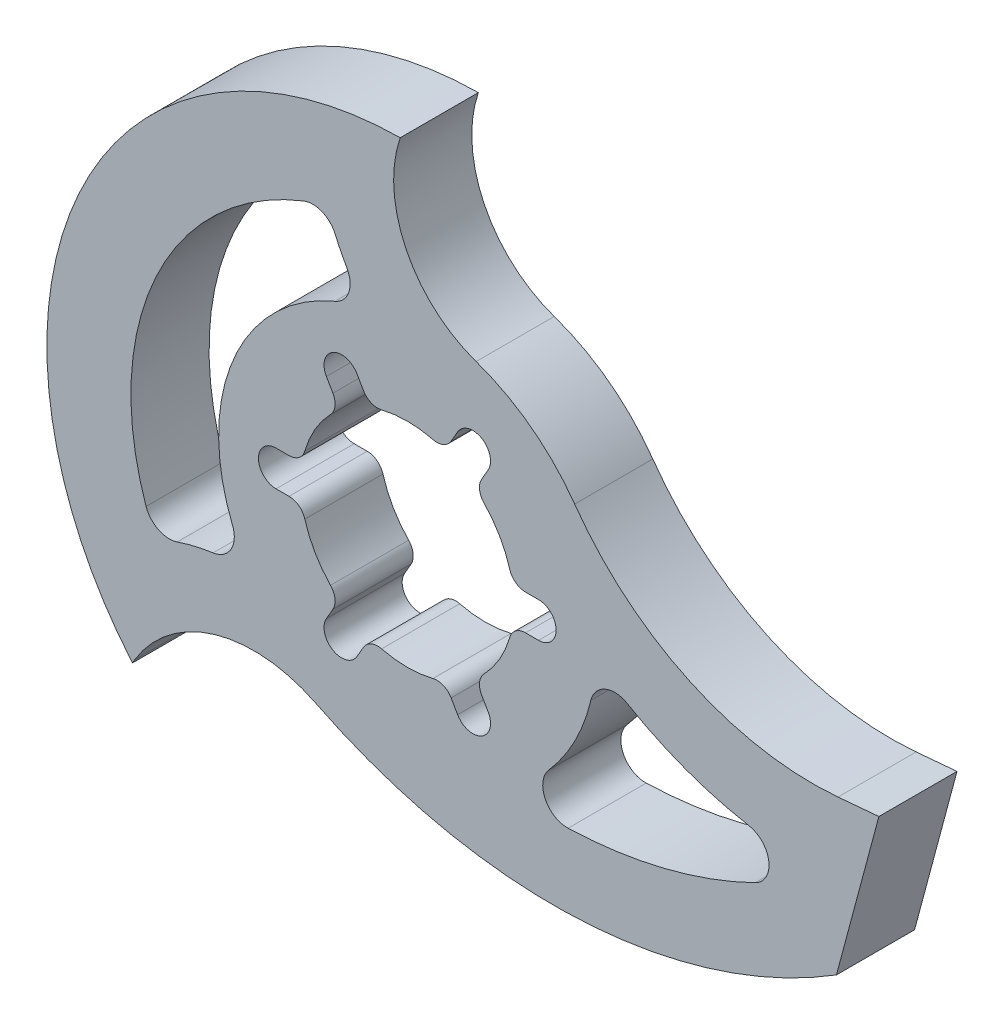
SolidWorks part; units mm, degrees
material "Alloy Steel"
ref_plane "Front Plane" through (0, 0, 0) normal (0, 0, 1) x (1, 0, 0)
ref_plane "Top Plane" through (0, 0, 0) normal (0, 1, 0) x (1, 0, 0)
ref_plane "Right Plane" through (0, 0, 0) normal (1, 0, 0) x (0, 0, -1)
sketch "Sketch1" plane through (0, 0, 0) normal (0, 0, 1) x (1, 0, 0)
  line L0 (0, 0) -> (57.5, 0) construction
  line L1 (57.5, 0) -> (52.3236, -19.3185)
  line L2 (0, 0) -> (-40.042, 16.9968) construction
  line L3 (0, 0) -> (-0.861, 42.4913) construction
  line L4 (0, 0) -> (-33.5025, -29.2888) construction
  line L5 (57.5, 0) -> (52.519, -0.4358)
  line L6 (-33.5025, -29.2888) -> (-36.2461, -34.2713) construction
  line L7 (-0.861, 42.4913) -> (1.5534, 49.5674) construction
  circle A0 centre (0, 0) radius 57.5 construction
  circle A2 centre (0, 0) radius 16 construction
  circle A3 centre (0, 0) radius 13 construction
  circle A4 centre (0, 0) radius 44.5 construction
  arc A5 (-0.861, 42.4913) -> (-33.5025, -29.2888) centre (-0.4386, -1.0126) ccw
  arc A6 (-33.5025, -29.2888) -> (-33.235, -28.8228) centre (-20.3629, -36.5241) cw
  arc A7 (-0.861, 42.4913) -> (8.3945, 23.4847) centre (13.3355, 37.6476) ccw
  arc A8 (52.519, -0.4358) -> (20.4072, 14.4411) centre (49.4212, 34.9727) cw
  arc A9 (-33.235, -28.8228) -> (-11.1617, -22.37) centre (-18.7157, -37.5095) cw
  arc A10 (-11.1617, -22.37) -> (52.3236, -19.3185) centre (17.8587, 35.792) ccw
  circle A11 centre (0, 0) radius 25 construction
  arc A12 (8.3945, 23.4847) -> (20.4072, 14.4411) centre (0.2673, 0.1892) cw
  point P3 (51.4405, -19.3185)
  point P6 (-9.7502, -22.7382)
  point P27 (0, 0)
  point P28 (7.4098, 24.0096)
  point P30 (-5.8116, -21.7365)
  point P31 (0, 0)
  point P32 (-9.7502, -22.7382)
  dimension "D1" = 115
  dimension "D4" = 32
  dimension "D5" = 26
  dimension "D6" = 13
  dimension "D10" = 20
  dimension "D11" = 20
  dimension "D12" = 5
  dimension "D13" = 50
  dimension "D16" = 15
  dimension "D17" = 15
  dimension "D18" = 65
  dimension "D2" = 20
  dimension "D3" = 75
  dimension "D7" = 14
  dimension "D8" = 15
  dimension "D9" = 5
  dimension "D14" = 157
  dimension "D15" = 130
extrude "Boss-Extrude1" add sketch "Sketch1" along normal blind 9.525
sketch "Sketch2" plane through (0, 0, 9.525) normal (0, 0, 1) x (1, 0, 0)
  line L0 (0, 0) -> (57.5, 0) construction
  line L1 (16, -2.15) -> (14.4145, -2.15)
  line L2 (16, 2.15) -> (14.4145, 2.15)
  line L3 (9.862, -12.7814) -> (9.0692, -11.4083)
  line L4 (6.138, -14.9314) -> (5.3453, -13.5583)
  line L5 (-6.138, -14.9314) -> (-5.3453, -13.5583)
  line L6 (-9.862, -12.7814) -> (-9.0692, -11.4083)
  line L7 (-16, -2.15) -> (-14.4145, -2.15)
  line L8 (-16, 2.15) -> (-14.4145, 2.15)
  line L9 (-9.862, 12.7814) -> (-9.0692, 11.4083)
  line L10 (-6.138, 14.9314) -> (-5.3453, 13.5583)
  line L11 (6.138, 14.9314) -> (5.3453, 13.5583)
  line L12 (9.862, 12.7814) -> (9.0692, 11.4083)
  arc A1 (16, 2.15) -> (16, -2.15) centre (16, 0) cw
  circle A2 centre (0, 0) radius 16 construction
  circle A3 centre (0, 0) radius 13 construction
  arc A4 (12.4926, 3.5967) -> (9.3611, 9.0205) centre (0, 0) ccw
  arc A5 (14.4145, -2.15) -> (12.4926, -3.5967) centre (14.4145, -4.15) ccw
  arc A6 (14.4145, 2.15) -> (12.4926, 3.5967) centre (14.4145, 4.15) cw
  arc A7 (9.0692, -11.4083) -> (9.3611, -9.0205) centre (10.8013, -10.4083) cw
  arc A8 (9.862, -12.7814) -> (6.138, -14.9314) centre (8, -13.8564) cw
  arc A9 (5.3453, -13.5583) -> (3.1315, -12.6172) centre (3.6132, -14.5583) ccw
  arc A10 (-5.3453, -13.5583) -> (-3.1315, -12.6172) centre (-3.6132, -14.5583) cw
  arc A11 (-6.138, -14.9314) -> (-9.862, -12.7814) centre (-8, -13.8564) cw
  arc A12 (-9.0692, -11.4083) -> (-9.3611, -9.0205) centre (-10.8013, -10.4083) ccw
  arc A13 (-14.4145, -2.15) -> (-12.4926, -3.5967) centre (-14.4145, -4.15) cw
  arc A14 (-16, -2.15) -> (-16, 2.15) centre (-16, 0) cw
  arc A15 (-14.4145, 2.15) -> (-12.4926, 3.5967) centre (-14.4145, 4.15) ccw
  arc A16 (-9.0692, 11.4083) -> (-9.3611, 9.0205) centre (-10.8013, 10.4083) cw
  arc A17 (-9.862, 12.7814) -> (-6.138, 14.9314) centre (-8, 13.8564) cw
  arc A18 (-5.3453, 13.5583) -> (-3.1315, 12.6172) centre (-3.6132, 14.5583) ccw
  arc A19 (5.3453, 13.5583) -> (3.1315, 12.6172) centre (3.6132, 14.5583) cw
  arc A20 (6.138, 14.9314) -> (9.862, 12.7814) centre (8, 13.8564) cw
  arc A21 (9.0692, 11.4083) -> (9.3611, 9.0205) centre (10.8013, 10.4083) ccw
  arc A22 (3.1315, 12.6172) -> (-3.1315, 12.6172) centre (0, 0) ccw
  arc A23 (-9.3611, 9.0205) -> (-12.4926, 3.5967) centre (0, 0) ccw
  arc A24 (-12.4926, -3.5967) -> (-9.3611, -9.0205) centre (0, 0) ccw
  arc A25 (-3.1315, -12.6172) -> (3.1315, -12.6172) centre (0, 0) ccw
  arc A26 (9.3611, -9.0205) -> (12.4926, -3.5967) centre (0, 0) ccw
  arc A27 (41.6295, -8.8843) -> (22.9833, -0.8767) centre (49.4212, 34.9727) cw
  arc A28 (11.6048, -19.8577) -> (42.4206, -14.5341) centre (17.8587, 35.792) ccw
  arc A29 (22.9833, -0.8767) -> (11.6048, -19.8577) centre (0, 0) cw
  arc A32 (20.4072, 14.4411) -> (52.519, -0.4358) centre (49.4212, 34.9727) ccw construction
  arc A34 (-11.1617, -22.37) -> (52.3236, -19.3185) centre (17.8587, 35.792) ccw construction
  arc A35 (-8.8187, 21.2422) -> (-21.3099, -8.6537) centre (0, 0) ccw
  arc A37 (-9.7042, 30.9265) -> (-30.6774, -14.8536) centre (-0.4386, -1.0126) ccw
  arc A38 (-0.861, 42.4913) -> (-33.5025, -29.2888) centre (-0.4386, -1.0126) ccw construction
  arc A39 (-30.6774, -14.8536) -> (-23.6754, -12.7538) centre (-20.3629, -36.5241) cw
  arc A40 (-9.7042, 30.9265) -> (-7.3796, 25.5279) centre (13.3355, 37.6476) ccw
  arc A41 (-8.8187, 21.2422) -> (-7.3796, 25.5279) centre (-9.969, 24.0129) ccw
  arc A42 (-23.6754, -12.7538) -> (-21.3099, -8.6537) centre (-24.0895, -9.7825) ccw
  arc A44 (-33.235, -28.8228) -> (-33.5025, -29.2888) centre (-20.3629, -36.5241) ccw construction
  arc A46 (-0.861, 42.4913) -> (8.3945, 23.4847) centre (13.3355, 37.6476) ccw construction
  arc A47 (41.6295, -8.8843) -> (42.4206, -14.5341) centre (41.1048, -11.838) cw
  point P16 (0, 0)
  point P63 (0, 0)
  dimension "D1" = 2.15
  dimension "D2" = 2
  dimension "D5" = 9
  dimension "D6" = 9
  dimension "D7" = 23
  dimension "D8" = 10.25
  dimension "D9" = 9
  dimension "D10" = 9
  dimension "D11" = 3
  dimension "D4" = 23
  dimension "D3" = 6
extrude "Cut-Extrude1" cut sketch "Sketch2" against normal through all
fillet "Fillet1" radius 3 4 edges at (22.9833, -0.8767, 4.7625) (11.6048, -19.8577, 4.7625) (-9.7042, 30.9265, 4.7625) (-30.6774, -14.8536, 4.7625)
